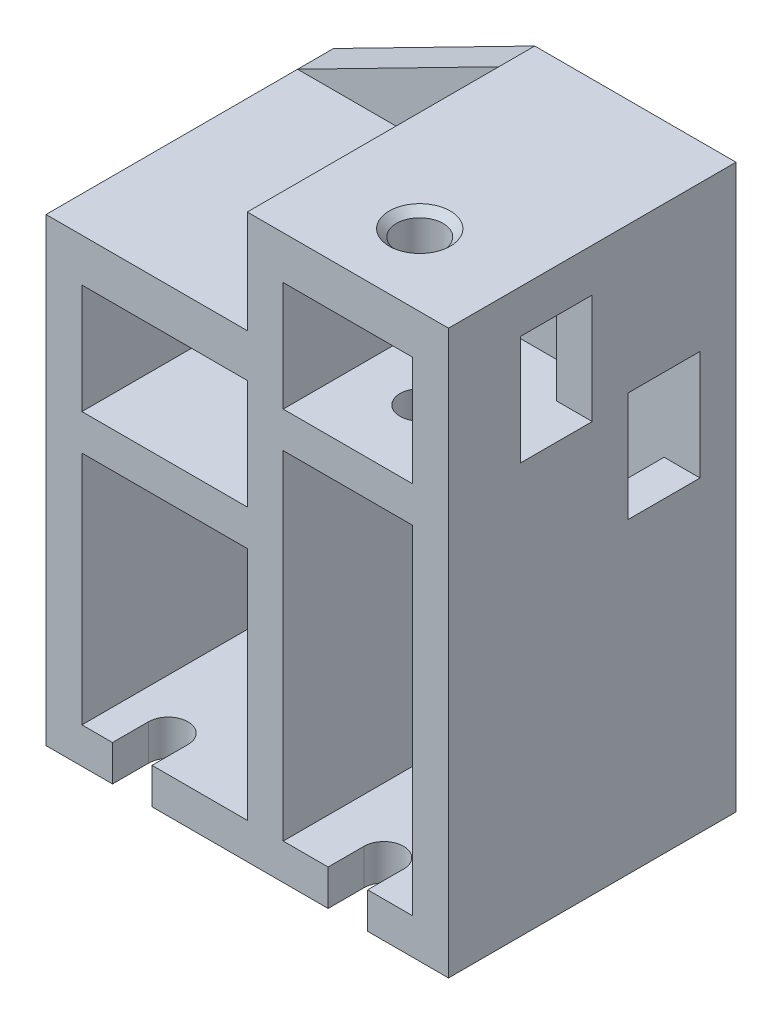
SolidWorks part; units mm, degrees
material "PET"
ref_plane "Front Plane" through (0, 0, 0) normal (0, 0, 1) x (1, 0, 0)
ref_plane "Top Plane" through (0, 0, 0) normal (0, 1, 0) x (1, 0, 0)
ref_plane "Right Plane" through (0, 0, 0) normal (1, 0, 0) x (0, 0, -1)
sketch "Sketch1" plane through (0, 0, 0) normal (0, 0, 1) x (1, 0, 0)
  line L0 (0, 0) -> (0, 64)
  line L1 (28, 78.3) -> (56, 78.3)
  line L2 (56, 78.3) -> (56, 0)
  line L4 (5, 5) -> (5, 37.75)
  line L6 (51, 72.3) -> (51, 57.05)
  line L7 (0, 64) -> (28, 64)
  line L9 (28, 58) -> (5, 58)
  line L10 (5, 42.75) -> (28, 42.75)
  line L11 (5, 5) -> (28, 5)
  line L12 (28, 37.75) -> (5, 37.75)
  line L13 (51, 57.05) -> (33, 57.05)
  line L14 (5, 42.75) -> (5, 58)
  line L15 (33, 52.05) -> (51, 52.05)
  line L18 (51, 52.05) -> (51, 5)
  line L20 (28, 64) -> (28, 58) construction
  line L21 (33, 57.05) -> (33, 72.3)
  line L22 (28, 64) -> (28, 78.3)
  line L23 (33, 72.3) -> (51, 72.3)
  line L24 (33, 52.05) -> (33, 5)
  line L25 (28, 58) -> (28, 42.75)
  line L27 (56, 0) -> (0, 0)
  line L28 (28, 37.75) -> (28, 5)
  line L29 (33, 5) -> (51, 5)
  point P20 (19, 42.75)
  point P22 (42, 57.05)
  dimension "D2" = 5
  dimension "D3" = 5
  dimension "D4" = 6
  dimension "D5" = 15.25
  dimension "D6" = 42.75
  dimension "D7" = 5
  dimension "D8" = 15.25
  dimension "D9" = 18
  dimension "D10" = 5
  dimension "D11" = 5
  dimension "D12" = 23
  dimension "D13" = 23
  dimension "D14" = 5
  dimension "D15" = 6
  dimension "D16" = 57.05
extrude "Boss-Extrude1" add sketch "Sketch1" along normal blind 40 contours L22 L7 L0 L4 L12 L10 L14 L9 L15 L18 L2 L1 L21 L23 L6 L13 region at (29.4792, 38.3716, 0)
sketch "Sketch2" plane through (0, 78.3, 0) normal (0, 1, 0) x (1, 0, 0)
  line L0 (28, -40) -> (56, -40) construction
  line L1 (56, -40) -> (56, 0) construction
  line L3 (0, 0) -> (28, 0) construction
  circle A0 centre (19, -15) radius 2.75
  circle A1 centre (42, -30) radius 2.75
  dimension "D1" = 23
  dimension "D2" = 5.5
  dimension "D3" = 5.5
  dimension "D4" = 14
  dimension "D5" = 10
  dimension "D6" = 15
extrude "Cut-Extrude1" cut sketch "Sketch2" against normal up to surface (40.55 mm away) up to face at (16.5, 37.75, 20)
sketch "Sketch3" plane through (56, 0, 0) normal (1, 0, 0) x (0, 0, -1)
  line L1 (-20, 72.3) -> (-30, 72.3)
  line L2 (-20, 72.3) -> (-20, 57.05)
  line L3 (-20, 57.05) -> (-30, 57.05)
  line L4 (-30, 72.3) -> (-30, 57.05)
  line L5 (0, 78.3) -> (0, 0) construction
  line L6 (-40, 72.3) -> (0, 72.3) construction
  dimension "D2" = 20
  dimension "D3" = 15.25
  dimension "D4" = 10
extrude "Cut-Extrude2" cut sketch "Sketch3" against normal up to next
sketch "Sketch4" plane through (5, 0, 0) normal (1, 0, 0) x (0, 0, -1)
  line L2 (-5, 42.75) -> (-5, 58)
  line L3 (-5, 58) -> (-15, 58)
  line L4 (-15, 42.75) -> (-15, 58)
  line L5 (0, 78.3) -> (0, 0) construction
  line L6 (-5, 42.75) -> (-15, 42.75)
  line L7 (-40, 42.75) -> (0, 42.75) construction
  dimension "D1" = 5
  dimension "D2" = 10
  dimension "D3" = 15.25
extrude "Cut-Extrude3" cut sketch "Sketch4" along normal through all
sketch "Sketch6" plane through (0, 78.3, 0) normal (0, 1, 0) x (1, 0, 0)
  circle A0 centre (19, -15) radius 3.25
  circle A1 centre (42, -30) radius 3.25
  dimension "D1" = 6.5
  dimension "D2" = 6.5
extrude "Cut-Extrude4" cut sketch "Sketch6" against normal up to next
ref_axis "Axis1" through (42, 72.3, 30) along (0, 1, 0)
ref_plane "Plane1" through (42, 0, 0) normal (1, 0, 0) x (0, 0, -1)
chamfer "Chamfer1" distance 1 angle 45 2 edges at (42, 78.3, 33.25) (19, 64, 18.25)
sketch "Sketch7" plane through (0, 0, 0) normal (0, -1, 0) x (1, 0, 0)
  line L0 (12, 40) -> (12, 0) construction
  line L1 (56, 40) -> (0, 40) construction
  line L2 (56, 0) -> (0, 0) construction
  line L3 (42, 40) -> (42, 0) construction
  line L5 (0, 40) -> (0, 0) construction
  line L7 (0, 15) -> (56, 15) construction
  line L8 (0, 35) -> (56, 35) construction
  line L9 (56, 40) -> (0, 40) construction
  line L10 (56, 0) -> (0, 0) construction
  line L11 (56, 40) -> (56, 0) construction
  line L12 (9.25, 35) -> (9.25, 40)
  line L13 (14.75, 35) -> (14.75, 40)
  line L14 (14.75, 40) -> (9.25, 40)
  line L15 (39.25, 35) -> (39.25, 40)
  line L16 (44.75, 35) -> (44.75, 40)
  line L17 (44.75, 40) -> (39.25, 40)
  arc A0 (9.25, 35) -> (14.75, 35) centre (12, 35) ccw
  arc A1 (39.25, 35) -> (44.75, 35) centre (42, 35) ccw
  circle A2 centre (12, 15) radius 3.3
  circle A3 centre (42, 15) radius 3.3
  dimension "D5" = 5.5
  dimension "D6" = 6.6
  dimension "D7" = 5.5
  dimension "D8" = 6.6
  dimension "D1" = 12
  dimension "D2" = 14
  dimension "D3" = 15
  dimension "D4" = 5
extrude "Cut-Extrude5" cut sketch "Sketch7" against normal up to next
sketch "Sketch9" plane through (0, 5, 0) normal (0, 1, 0) x (1, 0, 0)
  circle A0 centre (19, -15) radius 2.75
  dimension "D1" = 5.5
extrude "Cut-Extrude6" cut sketch "Sketch9" against normal through all
sketch "Sketch10" plane through (0, 0, 0) normal (0, 0, -1) x (-1, 0, 0)
  line L0 (-28, 78.3) -> (0, 64)
  line L1 (0, 64) -> (-28, 64)
  line L2 (-28, 64) -> (-28, 78.3)
  line L7 (-33, 52.05) -> (-33, 5) construction
  line L8 (-51, 52.05) -> (-33, 52.05)
  line L9 (-51, 52.05) -> (-51, 27.05)
  line L10 (-51, 27.05) -> (-33, 27.05)
  line L11 (-33, 52.05) -> (-33, 27.05)
  line L12 (-5, 5) -> (-5, 37.75) construction
  line L13 (-28, 37.75) -> (-5, 37.75)
  line L14 (-28, 37.75) -> (-28, 27.05)
  line L15 (-28, 27.05) -> (-5, 27.05)
  line L16 (-5, 37.75) -> (-5, 27.05)
  dimension "D1" = 25
extrude "Boss-Extrude2" add sketch "Sketch10" against normal blind 5
